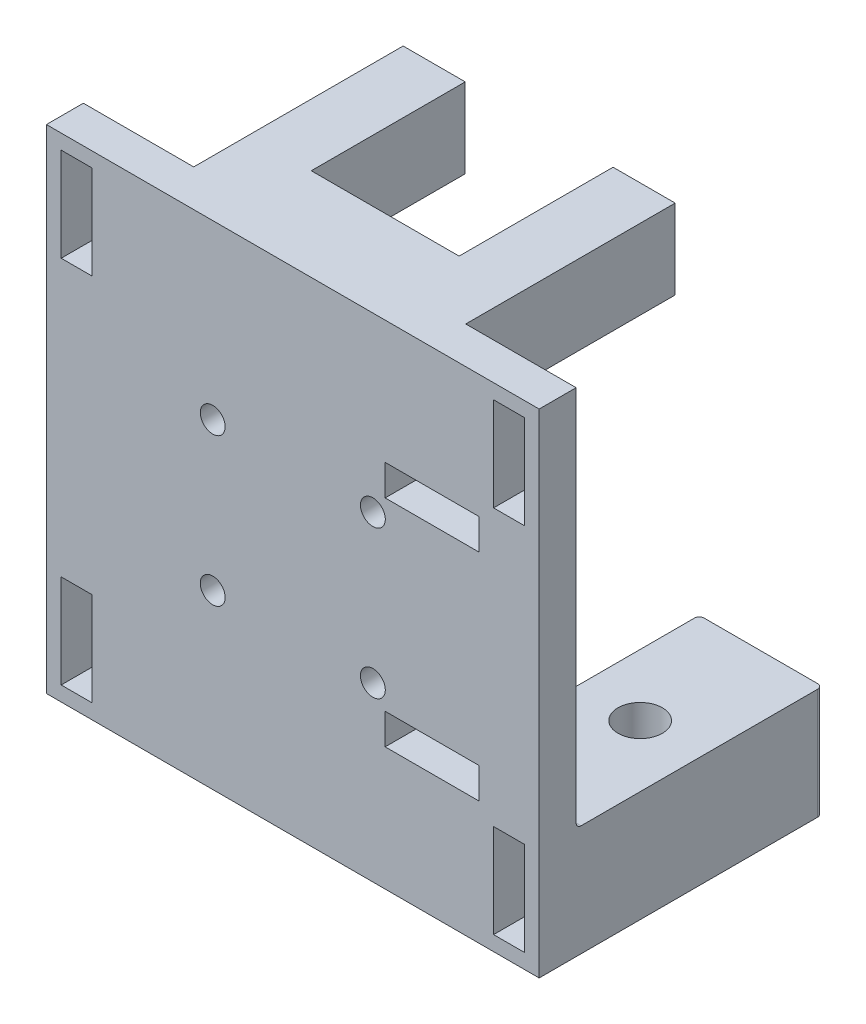
SolidWorks part; units mm, degrees
material "PET"
ref_plane "Alzado" through (0, 0, 0) normal (0, 0, 1) x (1, 0, 0)
ref_plane "Planta" through (0, 0, 0) normal (0, 1, 0) x (1, 0, 0)
ref_plane "Vista lateral" through (0, 0, 0) normal (1, 0, 0) x (0, 0, -1)
sketch "Sketch1" plane through (0, 0, 0) normal (0, 0, 1) x (1, 0, 0)
  line L0 (0, -1000) -> (0, 49000) construction
  line L5 (-1000, 0) -> (49000, 0) construction
  line L7 (-20, -20) -> (20, -20)
  line L8 (-20, -20) -> (-20, 20)
  line L9 (-20, 20) -> (20, 20)
  line L10 (20, -20) -> (20, 20)
  line L11 (-20, -20) -> (20, 20) construction
  line L12 (-20, 20) -> (20, -20) construction
  circle A0 centre (6.5, -6) radius 1.01
  circle A1 centre (-6.5, -6) radius 1.01
  circle A2 centre (6.5, 6) radius 1.01
  circle A3 centre (-6.5, 6) radius 1.01
  point P14 (0, 0)
  dimension "D3" = 2.02
  dimension "D1" = 6
  dimension "D2" = 6.5
  dimension "D4" = 40
  dimension "D5" = 40
extrude "Boss-Extrude1" add sketch "Sketch1" along normal blind 3
sketch "Sketch4" plane through (0, 0, 0) normal (0, 0, -1) x (-1, 0, 0)
  line L0 (20, 20) -> (20, -20) construction
  line L1 (-20, -20) -> (20, -20)
  line L2 (-20, -20) -> (-20, -11)
  line L3 (-20, -11) -> (20, -11)
  line L4 (20, -20) -> (20, -11)
  dimension "D1" = 9
extrude "Boss-Extrude2" add sketch "Sketch4" along normal blind 20
fillet "Fillet1" radius 0.4 1 edges at (0, -11, 0)
sketch "Sketch5" plane through (0, -11, 0) normal (0, 1, 0) x (1, 0, 0)
  line L0 (-20, 0.4) -> (20, 0.4) construction
  line L1 (-10, 20) -> (10, 20)
  line L2 (-10, 20) -> (-10, 0.4)
  line L3 (-10, 0.4) -> (10, 0.4)
  line L4 (10, 20) -> (10, 0.4)
  line L5 (-10, 20) -> (10, 0.4) construction
  line L6 (-10, 0.4) -> (10, 20) construction
  line L7 (-20, 20) -> (20, 20) construction
  line L8 (0, 20) -> (0, 0.4) construction
  line L9 (20, 20) -> (10, 0.4) construction
  circle A0 centre (15, 10.2) radius 1.8
  circle A1 centre (-15, 10.2) radius 1.8
  point P0 (0, 10.2)
  point P17 (15, 10.2)
  dimension "D2" = 3.6
  dimension "D1" = 20
extrude "Cut-Extrude2" cut sketch "Sketch5" against normal through all
sketch "Sketch2" plane through (0, 0, 3) normal (0, 0, 1) x (1, 0, 0)
  line L0 (0, 20) -> (0, -20) construction
  line L1 (20, 20) -> (-20, 20) construction
  line L2 (-20, -20) -> (20, -20) construction
  line L3 (-20, 0) -> (20, 0) construction
  line L4 (-20, 20) -> (-20, -20) construction
  line L5 (20, -20) -> (20, 20) construction
  line L6 (18.8, 11.2) -> (16.3, 11.2)
  line L7 (-18.8, 18.8) -> (-16.3, 18.8)
  line L8 (-18.8, 18.8) -> (-18.8, 11.2)
  line L9 (-18.8, 11.2) -> (-16.3, 11.2)
  line L10 (-16.3, 18.8) -> (-16.3, 11.2)
  line L23 (7.5, 10) -> (15.1, 10)
  line L24 (7.5, 10) -> (7.5, 7.5)
  line L25 (7.5, 7.5) -> (15.1, 7.5)
  line L26 (15.1, 10) -> (15.1, 7.5)
  line L31 (18.8, 18.8) -> (18.8, 11.2)
  line L32 (18.8, 18.8) -> (16.3, 18.8)
  line L33 (16.3, 18.8) -> (16.3, 11.2)
  line L34 (16.3, -18.8) -> (16.3, -11.2)
  line L35 (18.8, -18.8) -> (16.3, -18.8)
  line L36 (18.8, -18.8) -> (18.8, -11.2)
  line L37 (18.8, -11.2) -> (16.3, -11.2)
  line L38 (-18.8, -11.2) -> (-16.3, -11.2)
  line L39 (-18.8, -18.8) -> (-18.8, -11.2)
  line L40 (-18.8, -18.8) -> (-16.3, -18.8)
  line L41 (-16.3, -18.8) -> (-16.3, -11.2)
  line L42 (15.1, -10) -> (15.1, -7.5)
  line L43 (7.5, -7.5) -> (15.1, -7.5)
  line L44 (7.5, -10) -> (7.5, -7.5)
  line L45 (7.5, -10) -> (15.1, -10)
  point P36 (15.1, 8.75)
  dimension "D1" = 7.6
  dimension "D2" = 2.5
  dimension "D3" = 1.2
  dimension "D4" = 1.2
  dimension "D5" = 2.5
  dimension "D6" = 7.6
  dimension "D7" = 1.2
  dimension "D8" = 1.2
extrude "Cut-Extrude1" cut sketch "Sketch2" against normal through all
fillet "Fillet2" radius 0.4 6 edges at (-10, -15.5, -0.4) (10, -15.5, -0.4) (-10, -15.5, -20) (-20, -15.5, -20) (20, -15.5, -20) (10, -15.5, -20)
sketch "Sketch6" plane through (0, 0, 3) normal (0, 0, 1) x (1, 0, 0)
  line L0 (20, 20) -> (-20, 20) construction
  line L1 (-11.0418, 13.5369) -> (11.0418, 13.5369)
  line L2 (-11.0418, 13.5369) -> (-11.0418, 20)
  line L3 (-11.0418, 20) -> (11.0418, 20)
  line L4 (11.0418, 13.5369) -> (11.0418, 20)
  line L5 (-11.0418, 13.5369) -> (11.0418, 20) construction
  line L6 (-11.0418, 20) -> (11.0418, 13.5369) construction
  point P0 (0, 16.7685)
extrude "Boss-Extrude3" add sketch "Sketch6" against normal blind 20
sketch "Sketch7" plane through (0, 20, 0) normal (0, 1, 0) x (1, 0, 0)
  line L1 (-6, 4.5008) -> (6, 4.5008)
  line L2 (-6, 4.5008) -> (-6, 17)
  line L3 (-6, 17) -> (6, 17)
  line L4 (6, 4.5008) -> (6, 17)
  line L5 (-6, 4.5008) -> (6, 17) construction
  line L6 (-6, 17) -> (6, 4.5008) construction
  line L7 (11.0418, 17) -> (-11.0418, 17) construction
  point P0 (0, 10.7504)
  point P5 (0, 0)
  point P8 (0, 0)
  dimension "D1" = 12
extrude "Cut-Extrude3" cut sketch "Sketch7" against normal up to surface (6.4631 mm away) up to face at (0, 13.5369, -8.5)
